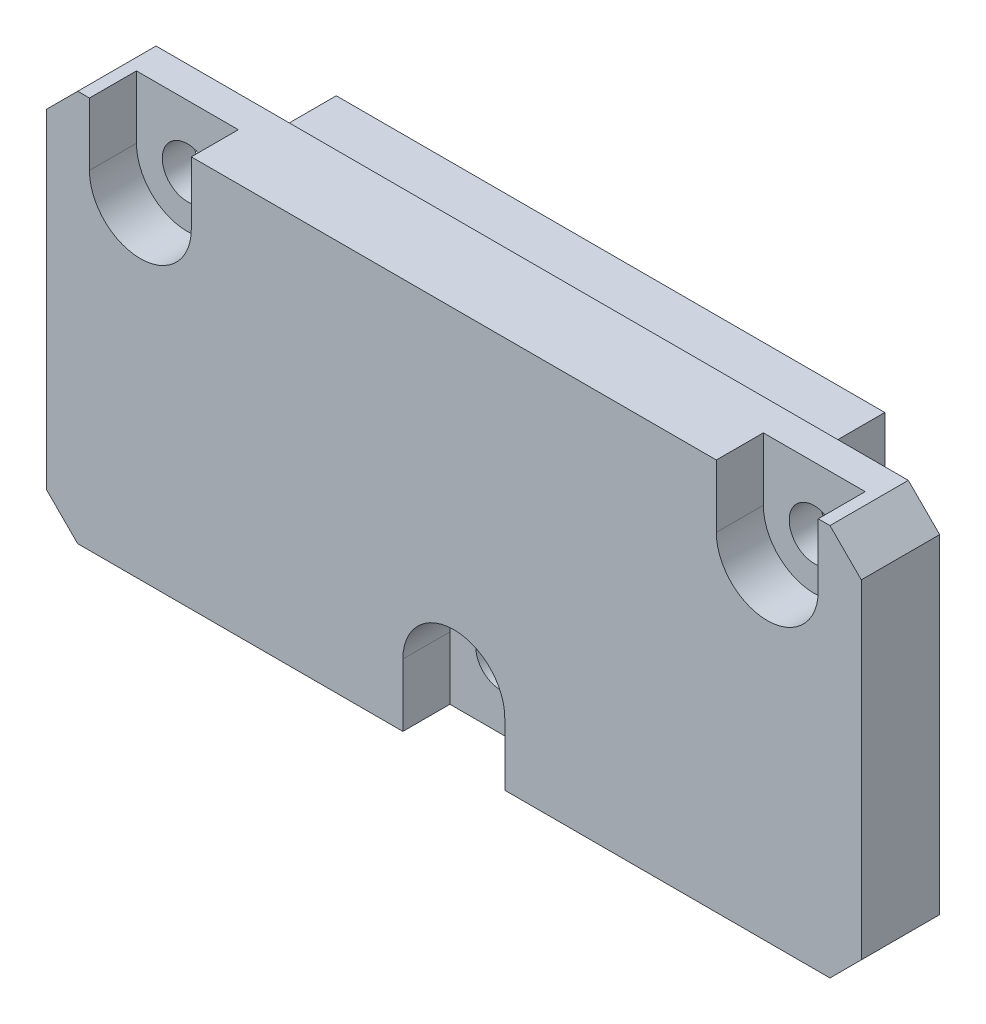
SolidWorks part; units mm, degrees
material "Сталь"
ref_plane "Спереди" through (0, 0, 0) normal (0, 0, 1) x (1, 0, 0)
ref_plane "Сверху" through (0, 0, 0) normal (0, 1, 0) x (1, 0, 0)
ref_plane "Справа" through (0, 0, 0) normal (1, 0, 0) x (0, 0, -1)
sketch "Эскиз1" plane through (0, 0, 0) normal (0, 0, 1) x (1, 0, 0)
  line L1 (-26, -12.5) -> (26, -12.5)
  line L2 (-26, -12.5) -> (-26, 12.5)
  line L3 (-26, 12.5) -> (26, 12.5)
  line L4 (26, -12.5) -> (26, 12.5)
  line L5 (-26, -12.5) -> (26, 12.5) construction
  line L6 (-26, 12.5) -> (26, -12.5) construction
  point P0 (0, 0)
  dimension "D1" = 52
  dimension "D2" = 25
extrude "Бобышка-Вытянуть1" add sketch "Эскиз1" along normal blind 5
chamfer "Фаска1" distance 2 angle 45 4 edges at (26, -12.5, 2.5) (-26, -12.5, 2.5) (-26, 12.5, 2.5) (26, 12.5, 2.5)
sketch "Эскиз2" plane through (0, 0, 0) normal (0, 0, -1) x (-1, 0, 0)
  line L0 (-17.5, 3) -> (17.5, 3) construction
  line L1 (-17.5, -4.5) -> (-17.5, 10.5) construction
  line L2 (17.5, 10.5) -> (17.5, -4.5) construction
  line L4 (17.5, -4.5) -> (-17.5, -4.5)
  line L5 (17.5, -4.5) -> (17.5, 10.5)
  line L6 (17.5, 10.5) -> (-17.5, 10.5)
  line L7 (-17.5, -4.5) -> (-17.5, 10.5)
  line L8 (17.5, -4.5) -> (-17.5, 10.5) construction
  line L9 (17.5, 10.5) -> (-17.5, -4.5) construction
  point P6 (0, 3)
extrude "Бобышка-Вытянуть2" add sketch "Эскиз2" along normal blind 5
sketch "Эскиз3" plane through (0, 0, 5) normal (0, 0, 1) x (1, 0, 0)
  line L0 (-24, -12.5) -> (24, -12.5) construction
  line L1 (-3.25, -8.5) -> (-3.25, -12.5)
  line L2 (-3.25, -12.5) -> (3.25, -12.5)
  line L3 (3.25, -12.5) -> (3.25, -8.5)
  line L4 (26, -10.5) -> (26, 10.5) construction
  line L5 (-26, 10.5) -> (-26, -10.5) construction
  line L6 (24, 12.5) -> (-24, 12.5) construction
  line L7 (-23.25, 8.5) -> (-23.25, 12.5)
  line L8 (-23.25, 12.5) -> (-16.75, 12.5)
  line L9 (-16.75, 12.5) -> (-16.75, 8.5)
  line L10 (16.75, 8.5) -> (16.75, 12.5)
  line L12 (23.25, 8.5) -> (23.25, 12.5)
  line L13 (23.25, 12.5) -> (16.75, 12.5)
  circle A0 centre (0, -8.5) radius 3.25
  circle A1 centre (-20, 8.5) radius 3.25
  circle A2 centre (20, 8.5) radius 3.25
  line M1 (-24, -12.5) -> (24, -12.5)
  line M5 (24, 12.5) -> (-24, 12.5)
  dimension "D1" = 6.5
  dimension "D2" = 4
  dimension "D3" = 6
  dimension "D4" = 6
  dimension "D5" = 4
extrude "Вырез-Вытянуть1" cut sketch "Эскиз3" against normal blind 3 contours A0 | A0 L1 L3 M1 | A1 L9 L7 M5 | A1 | A2 | A2 L12 L10 M5 region at (0, -11.8263, 5) region at (0, -8.5, 5) region at (20, 12.4237, 5) region at (-23.1737, 10.5, 5) region at (-20, 8.5, 5) region at (20, 8.5, 5)
sketch "Эскиз5" plane through (0, 0, 2) normal (0, 0, 1) x (1, 0, 0)
  circle A0 centre (0, -8.5) radius 1.6
  circle A1 centre (-20, 8.5) radius 1.6
  circle A2 centre (20, 8.5) radius 1.6
  dimension "D1" = 3.2
extrude "Вырез-Вытянуть2" cut sketch "Эскиз5" against normal through all
